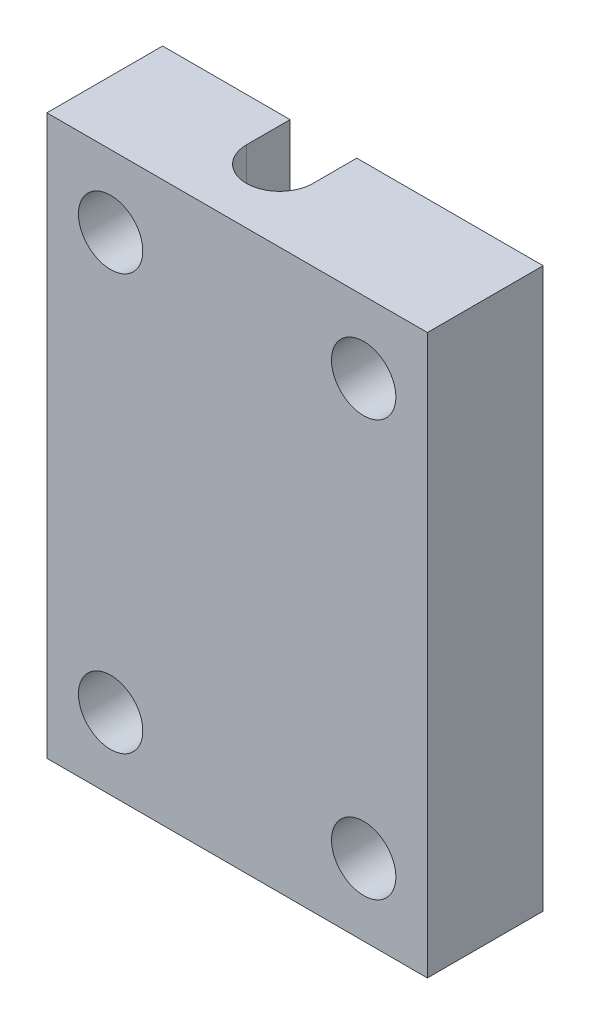
SolidWorks part; units mm, degrees
ref_plane "Front Plane" through (0, 0, 0) normal (0, 0, 1) x (1, 0, 0)
ref_plane "Top Plane" through (0, 0, 0) normal (0, 1, 0) x (1, 0, 0)
ref_plane "Right Plane" through (0, 0, 0) normal (1, 0, 0) x (0, 0, -1)
sketch "Sketch1" plane through (0, 0, 0) normal (0, 1, 0) x (1, 0, 0)
  line L0 (-9.7, 0) -> (-3.2, 0)
  line L1 (-9.7, 0) -> (-9.7, -5.9)
  line L2 (9.7, -5.9) -> (9.7, 0)
  line L19 (0.2, 0) -> (9.7, 0)
  line L21 (-3.2, -2.23) -> (-3.2, 0)
  line L27 (0.2, -2.23) -> (0.2, 0)
  line L28 (-9.7, -5.9) -> (9.7, -5.9)
  arc A2 (-3.2, -2.23) -> (0.2, -2.23) centre (-1.5, -2.23) ccw
extrude "Boss-Extrude1" add sketch "Sketch1" along normal blind 28.5
sketch "Sketch2" plane through (0, 0, 0) normal (0, 0, -1) x (-1, 0, 0)
  circle A1 centre (6.45, 24.8442) radius 1.64
  circle A2 centre (6.45, 3.6558) radius 1.64
  circle A3 centre (-6.45, 3.6558) radius 1.64
  circle A4 centre (-6.45, 24.8442) radius 1.64
extrude "Cut-Extrude1" cut sketch "Sketch2" against normal up to surface (5.9 mm away) up to face at (0, 14.25, 5.9)
sketch "Sketch4" plane through (0, 0, 0) normal (0, 0, -1) x (-1, 0, 0)
  line L7 (3.2, 17.2013) -> (3.2, 16.1683)
  line L9 (-0.2, 17.2013) -> (-0.2, 16.1683)
  line L12 (3.2, 12.3317) -> (3.2, 11.2987)
  line L13 (-0.2, 12.3317) -> (-0.2, 11.2987)
  arc A0 (-0.2593, 16.0262) -> (-0.2593, 12.4738) centre (1.5, 14.25) ccw
  arc A2 (3.2593, 12.4738) -> (3.2593, 16.0262) centre (1.5, 14.25) ccw
  arc A5 (3.2593, 12.4738) -> (3.2, 12.3317) centre (3.4, 12.3317) ccw
  arc A7 (-0.2593, 12.4738) -> (-0.2, 12.3317) centre (-0.4, 12.3317) cw
  arc A8 (-0.2593, 16.0262) -> (-0.2, 16.1683) centre (-0.4, 16.1683) ccw
  arc A10 (3.2, 16.1683) -> (3.2593, 16.0262) centre (3.4, 16.1683) ccw
  arc A12 (-0.5083, 17.3695) -> (-0.5083, 11.1305) centre (1.5, 14.25) ccw
  arc A13 (3.5083, 11.1305) -> (3.5083, 17.3695) centre (1.5, 14.25) ccw
  arc A14 (3.5083, 11.1305) -> (3.2, 11.2987) centre (3.4, 11.2987) cw
  arc A15 (-0.5083, 11.1305) -> (-0.2, 11.2987) centre (-0.4, 11.2987) ccw
  arc A16 (-0.5083, 17.3695) -> (-0.2, 17.2013) centre (-0.4, 17.2013) cw
  arc A17 (3.2, 17.2013) -> (3.5083, 17.3695) centre (3.4, 17.2013) cw
extrude "Boss-Extrude2" add sketch "Sketch4" along normal blind 0.5
sketch "Sketch5" plane through (0, 0, -0.5) normal (0, 0, -1) x (-1, 0, 0)
  circle A6 centre (1.5, 14.25) radius 2.5
extrude "Cut-Extrude3" cut sketch "Sketch5" against normal blind 4.4
